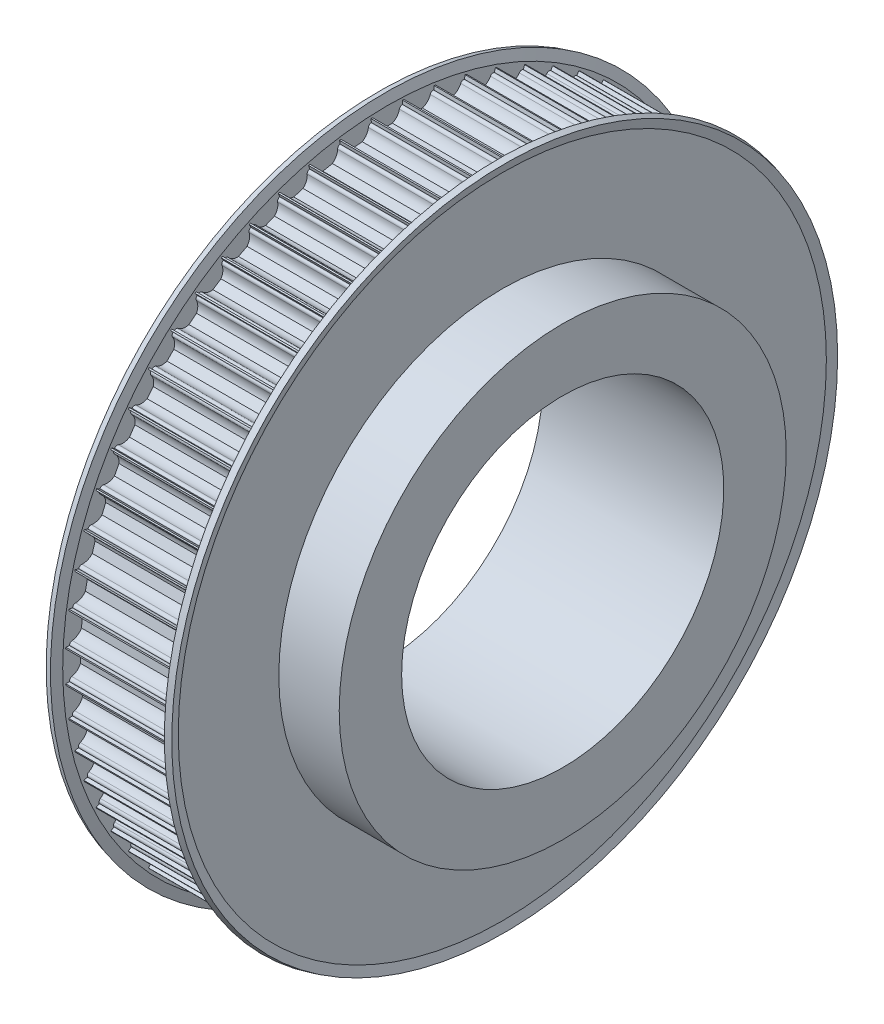
SolidWorks part; units mm, degrees
material "Zinc AC43A (Zn-4Al-2.5Cu-0.04Mg; Number 2 Die Casting Alloy; Zamak 2), Die Cast"
ref_plane "Front Plane" through (0, 0, 0) normal (0, 0, 1) x (1, 0, 0)
ref_plane "Top Plane" through (0, 0, 0) normal (0, 1, 0) x (1, 0, 0)
ref_plane "Right Plane" through (0, 0, 0) normal (1, 0, 0) x (0, 0, -1)
sketch "Sketch1" plane through (0, 0, 0) normal (0, 0, 1) x (1, 0, 0)
  line L0 (-22.9139, 0) -> (27.5073, 0) construction
  line L1 (0, 40) -> (45, 40)
  line L2 (45, 40) -> (45, 55.5)
  line L3 (45, 55.5) -> (30, 55.5)
  line L4 (30, 55.5) -> (30, 80)
  line L5 (30, 80) -> (0, 80)
  line L6 (0, 80) -> (0, 40)
  point P10 (22.5, 40)
  dimension "D1" = 80
  dimension "D2" = 15.5
  dimension "D3" = 15
  dimension "D4" = 30
  dimension "D5" = 40
revolve "Revolve1" add sketch "Sketch1" angle 360 about L0
sketch "Sketch2" plane through (0, 0, 0) normal (-1, 0, 0) x (0, 0, 1)
  line L0 (3.6742, 79) -> (3.75, 79)
  line L1 (-3.75, 81) -> (3.75, 81)
  line L2 (-3.75, 81) -> (-3.75, 79)
  line L3 (-3.75, 79) -> (-3.6742, 79)
  line L4 (3.75, 81) -> (3.75, 79)
  line L5 (-1.199, 76.25) -> (1.199, 76.25)
  line L6 (0, 29.8133) -> (0, 24.9397) construction
  arc A0 (2.9394, 78.4) -> (1.199, 76.25) centre (0, 79) cw
  arc A1 (-1.199, 76.25) -> (-2.9394, 78.4) centre (0, 79) cw
  arc A2 (2.9394, 78.4) -> (3.6742, 79) centre (3.6742, 78.25) cw
  arc A3 (-2.9394, 78.4) -> (-3.6742, 79) centre (-3.6742, 78.25) ccw
  point P3 (0, 79)
  point P10 (3, 79)
  point P14 (-3, 79)
  dimension "D3" = 3
  dimension "D6" = 0.75
  dimension "D1" = 2
  dimension "D2" = 7.5
  dimension "D4" = 79
  dimension "D5" = 2.75
extrude "Cut-Extrude1" cut sketch "Sketch2" against normal up to next
pattern_circular "CirPattern1" count 64 over 360 about axis through (-22.9139, 0, 0) along (-1, 0, 0) of "Cut-Extrude1"
sketch "Sketch3" plane through (0, 0, 0) normal (0, 0, 1) x (1, 0, 0)
  line L0 (1.5, 80.6621) -> (0.0511, 80.2738) construction
  line L1 (0, 80.6621) -> (1.5, 80.6621) construction
  line L2 (0, 80.6621) -> (0, 75.6621)
  line L3 (0, 75.6621) -> (1.5, 75.6621)
  line L4 (1.5, 80.6621) -> (1.5, 75.6621)
  line L5 (1.5, 80.6621) -> (0.8569, 83.0621)
  line L6 (0.0511, 80.2738) -> (-0.592, 82.6738)
  line L7 (0.8569, 83.0621) -> (-0.592, 82.6738)
  line L8 (0, 79.9121) -> (30, 79.9121) construction
  line L9 (0, -39.5498) -> (0, -40.4807) construction
  line L10 (15, -40.9775) -> (15, -28.3327) construction
  line L11 (30, -40.9775) -> (0, -40.9775) construction
  line L12 (30, 80.6621) -> (28.5, 80.6621) construction
  line L13 (28.5, 80.6621) -> (29.9489, 80.2738) construction
  line L14 (29.1431, 83.0621) -> (30.592, 82.6738)
  line L15 (29.9489, 80.2738) -> (30.592, 82.6738)
  line L16 (28.5, 80.6621) -> (29.1431, 83.0621)
  line L17 (28.5, 80.6621) -> (28.5, 75.6621)
  line L18 (30, 75.6621) -> (28.5, 75.6621)
  line L19 (30, 80.6621) -> (30, 75.6621)
  dimension "D1" = 1.5
  dimension "D2" = 5
  dimension "D3" = 1.5
  dimension "D4" = 165
  dimension "D5" = 2.4
  dimension "D6" = 0.75
revolve "Revolve2" add sketch "Sketch3" angle 360 about axis through (-22.9139, 0, 0) along (-1, 0, 0) region at (0.6556, 79.2932, 0) region at (29.3444, 79.2932, 0)
